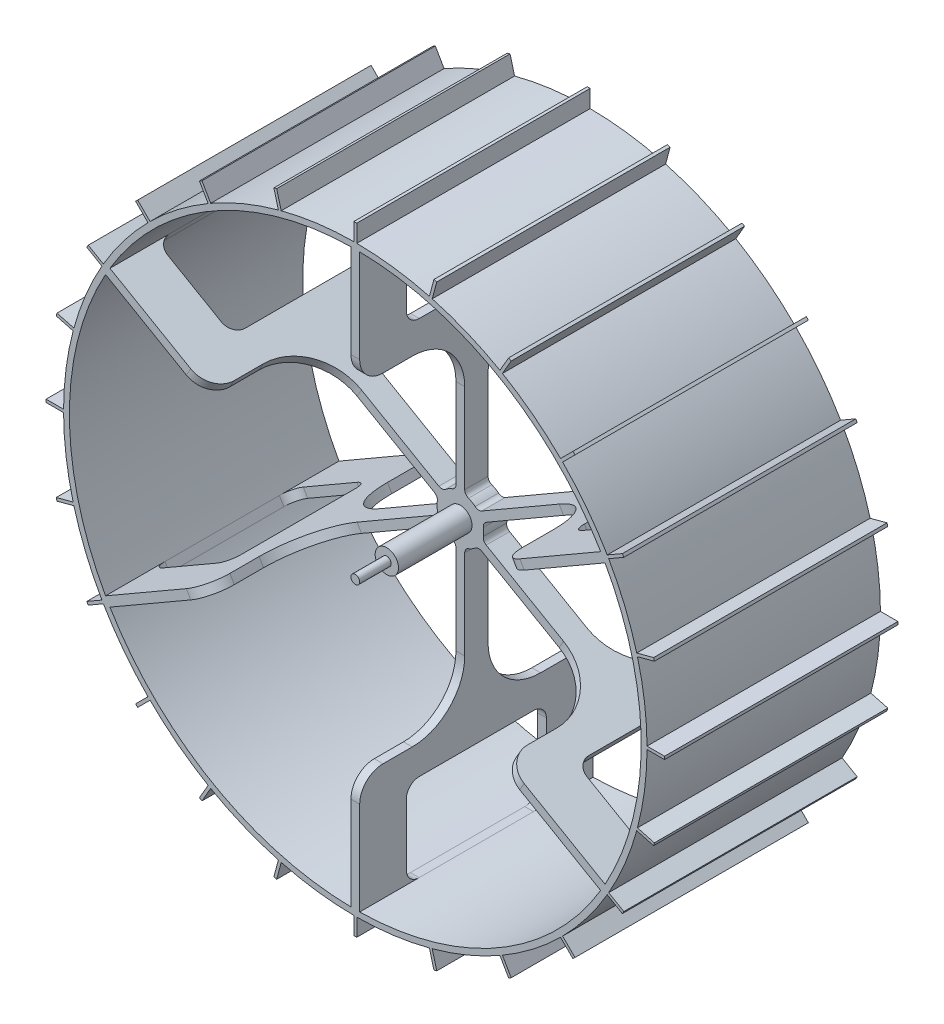
SolidWorks part; units mm, degrees
material "7075-O (SS)"
ref_plane "Front Plane" through (0, 0, 0) normal (0, 0, 1) x (1, 0, 0)
ref_plane "Top Plane" through (0, 0, 0) normal (0, 1, 0) x (1, 0, 0)
ref_plane "Right Plane" through (0, 0, 0) normal (1, 0, 0) x (0, 0, -1)
sketch "Sketch1" plane through (0, 0, 0) normal (0, 0, 1) x (1, 0, 0)
  circle A0 centre (0, 0) radius 500
  dimension "D1" = 1000
extrude "Wheel Base" add sketch "Sketch1" along normal blind 400
ref_axis "Axis1" through (0, 0, 1218.9124) along (0, 0, -1)
sketch "Sketch3" plane through (0, 0, 0) normal (0, 1, 0) x (1, 0, 0)
  line L0 (0, 0) -> (0, -400) construction
  line L2 (2.5, -400) -> (-2.5, -400)
  line L3 (2.5, -400) -> (2.5, 0)
  line L4 (2.5, 0) -> (-2.5, 0)
  line L5 (-2.5, -400) -> (-2.5, 0)
  line L6 (2.5, -400) -> (-2.5, 0) construction
  line L7 (2.5, 0) -> (-2.5, -400) construction
  point P3 (0, -200)
  dimension "D1" = 400
  dimension "D2" = 400
  dimension "D3" = 5
extrude "Grouser" add sketch "Sketch3" along normal blind 530
pattern_circular "Grousers" count 24 over 360 about axis through (0, 0, 1218.9124) along (0, 0, -1) of "Grouser"
sketch "Sketch4" plane through (0, 0, 400) normal (0, 0, 1) x (1, 0, 0)
  circle A0 centre (0, 0) radius 40
  circle A1 centre (0, 0) radius 500
  circle A2 centre (0, 0) radius 490
  dimension "D1" = 10
  dimension "D2" = 80
extrude "Bore" cut sketch "Sketch4" against normal through all contours A2 A0 region at (-476.1407, 0, 400)
ref_plane "Midplane" through (0, 0, 200) normal (0, 0, 1) x (1, 0, 0)
sketch "Sketch5" plane through (0, 0, 200) normal (0, 0, 1) x (1, 0, 0)
  line L0 (0, 0) -> (0, 490) construction
  line L2 (-7.5, 0) -> (7.5, 0)
  line L3 (-7.5, 0) -> (-7.5, 490)
  line L4 (-7.5, 490) -> (7.5, 490)
  line L5 (7.5, 0) -> (7.5, 490)
  line L6 (-7.5, 0) -> (7.5, 490) construction
  line L7 (-7.5, 490) -> (7.5, 0) construction
  circle A0 centre (0, 0) radius 490 construction
  point P6 (0, 245)
  dimension "D1" = 15
extrude "Boss-Extrude1" add sketch "Sketch5" along normal mid plane 40 contours L2 L5 L4 L0 | L4 L3 L2 L0 region at (0, 245, 200)
sketch "Sketch7" plane through (0, 0, 200) normal (0, 0, 1) x (1, 0, 0)
  line L2 (-7.5, 489.9426) -> (-7.5, 39.2906)
  line L3 (-7.5, 289.9426) -> (7.5, 289.9426)
  line L4 (-7.5, 489.9426) -> (-7.5, 39.2906)
  line L8 (7.5, 39.2906) -> (7.5, 489.9426)
  line L11 (7.5, 289.9426) -> (7.5, 489.9426)
  arc A2 (7.5, 489.9426) -> (-7.5, 489.9426) centre (0, 0) ccw
  arc A3 (7.5, 489.9426) -> (-7.5, 489.9426) centre (0, 0) ccw
  arc A4 (7.5, 39.2906) -> (-7.5, 39.2906) centre (0, 0) ccw
  arc A5 (7.5, 39.2906) -> (-7.5, 39.2906) centre (0, 0) ccw
  point P0 (-7.5, 289.9426)
  dimension "D2" = 200
extrude "Boss-Extrude4" add sketch "Sketch7" along normal mid plane 400 contours L11 A3 L4 L3 region at (0, 389.9617, 200)
fillet "Fillet1" radius 90 2 edges at (0, 289.9426, 180) (0, 289.9426, 220)
fillet "Fillet2" radius 40 2 edges at (0, 289.9426, 0) (0, 289.9426, 400)
sketch "Sketch8" plane through (7.5, 0, 0) normal (1, 0, 0) x (0, 0, -1)
  line L0 (-200, 489.9426) -> (-200, 12.5296) construction
  line L1 (0, 489.9426) -> (-400, 489.9426) construction
  line L3 (-320, 339.9426) -> (-80, 339.9426)
  line L4 (-320, 339.9426) -> (-320, 489.9426)
  line L5 (-320, 489.9426) -> (-80, 489.9426)
  line L6 (-80, 339.9426) -> (-80, 489.9426)
  line L7 (-320, 339.9426) -> (-80, 489.9426) construction
  line L8 (-320, 489.9426) -> (-80, 339.9426) construction
  point P4 (-200, 414.9426)
  dimension "D3" = 240
  dimension "D1" = 150
extrude "Cut-Extrude2" cut sketch "Sketch8" against normal up to surface (15 mm away) up to face at (-7.5, 274.8932, 200)
fillet "Fillet3" radius 22 4 edges at (0, 339.9426, 80) (0, 339.9426, 320) (0, 489.9426, 320) (0, 489.9426, 80)
pattern_circular "CirPattern1" count 6 over 360 about axis through (0, 0, 1218.9124) along (0, 0, -1) of "Boss-Extrude1", "Fillet1", "Boss-Extrude4", "Fillet2", "Cut-Extrude2", "Fillet3"
sketch "Sketch9" plane through (0, 0, 0) normal (0, 0, -1) x (-1, 0, 0)
  circle A0 centre (0, 0) radius 40 construction
  circle A1 centre (0, 0) radius 40
extrude "Shorten Bore" cut sketch "Sketch9" against normal up to surface (180 mm away) up to face at (0, 119.7939, 180)
sketch "Sketch10" plane through (0, 0, 400) normal (0, 0, 1) x (1, 0, 0)
  circle A0 centre (0, 0) radius 40
  circle A1 centre (0, 0) radius 40 construction
  circle A2 centre (0, 0) radius 20
  dimension "D1" = 40
extrude "Narrow Bore" cut sketch "Sketch10" against normal up to surface (180 mm away)
fillet "Fillet4" radius 10 12 edges at (37.7766, 13.1501, 200) (37.7766, -13.1501, 200) (-30.2766, 26.1405, 200) (30.2766, -26.1405, 200) (7.5, -39.2906, 200) (-7.5, -39.2906, 200) (-30.2766, -26.1405, 200) (-37.7766, -13.1501, 200) (-37.7766, 13.1501, 200) (-7.5, 39.2906, 200) (30.2766, 26.1405, 200) (7.5, 39.2906, 200)
sketch "Sketch11" plane through (0, 0, 400) normal (0, 0, 1) x (1, 0, 0)
  circle A0 centre (0, 0) radius 7.5
  circle A1 centre (0, 0) radius 20
  circle A2 centre (0, 0) radius 20 construction
  dimension "D1" = 15
extrude "Motor Shaft" cut sketch "Sketch11" against normal blind 54
ref_plane "Plane1" through (0, -530, 0) normal (0, -1, 0) x (-1, 0, 0)
equation "\"Wheel_Diameter\" = 100cm"
equation "\"D1@Sketch1\"=\"Wheel_Diameter\""
equation "\"Wheel_Width\" = 40cm"
equation "\"D1@Wheel Base\"=\"Wheel_Width\""
equation "\"D1@Sketch3\"=\"Wheel_Width\""
equation "\"D2@Sketch3\"=\"Wheel_Width\""
equation "\"Grouser_width\"= 5mm"
equation "\"D3@Sketch3\"=\"Grouser_width\""
equation "\"Grouser_height\"= 3cm"
equation "\"D1@Grouser\" = \"Wheel_Diameter\" / 2 + \"Grouser_height\""
equation "\"Number_of_Grousers\" = 24"
equation "\"D1@Grousers\" = \"Number_of_Grousers\""
equation "\"D1@Boss-Extrude4\"=\"Wheel_Width\""
equation "\"D2@Sketch7\"= \"Wheel_Diameter\" * .2"
equation "\"D1@Sketch8\" = \"Wheel_Diameter\" * .15"
equation "\"D3@Sketch8\"= \"Wheel_Width\" * .6"
